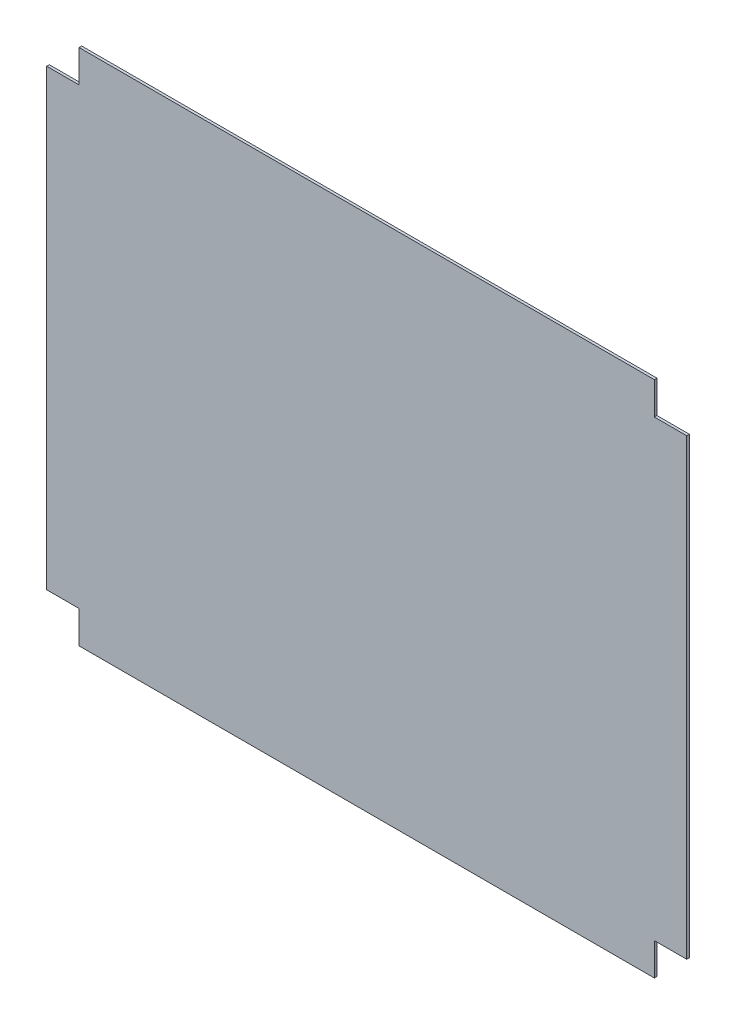
SolidWorks part; units mm, degrees
ref_plane "Front Plane" through (0, 0, 0) normal (0, 0, 1) x (1, 0, 0)
ref_plane "Top Plane" through (0, 0, 0) normal (0, 1, 0) x (1, 0, 0)
ref_plane "Right Plane" through (0, 0, 0) normal (1, 0, 0) x (0, 0, -1)
sketch "Çizim1" plane through (0, 0, 0) normal (0, 0, 1) x (1, 0, 0)
  line L1 (-247, 400) -> (247, 400)
  line L2 (-247, 400) -> (-247, 0)
  line L3 (-247, 0) -> (247, 0)
  line L4 (247, 400) -> (247, 0)
  point P4 (0, 0)
  dimension "D1" = 494
  dimension "D2" = 400
base flange "Taban-Flanş1" sketch "Çizim1" thickness 2 reverse thickness direction no parameters "D1"=0.7366
sketch "Çizim6" plane through (0, 0, 0) normal (0, 0, 1) x (1, 0, 0)
  line L0 (0, 0) -> (0, 141.4283) construction
  line L1 (-247, 400) -> (-222, 400)
  line L2 (-247, 400) -> (-247, 375)
  line L3 (-247, 375) -> (-222, 375)
  line L4 (-222, 400) -> (-222, 375)
  line L5 (-247, 200) -> (-327.7309, 200) construction
  line L6 (-247, 400) -> (-247, 0) construction
  line L7 (247, 400) -> (247, 375)
  line L8 (247, 400) -> (222, 400)
  line L9 (222, 400) -> (222, 375)
  line L10 (247, 375) -> (222, 375)
  line L11 (247, 25) -> (222, 25)
  line L12 (222, 0) -> (222, 25)
  line L13 (247, 0) -> (222, 0)
  line L14 (247, 0) -> (247, 25)
  line L15 (-222, 0) -> (-222, 25)
  line L16 (-247, 25) -> (-222, 25)
  line L17 (-247, 0) -> (-247, 25)
  line L18 (-247, 0) -> (-222, 0)
  dimension "D1" = 25
  dimension "D2" = 25
extrude "Kes-Ekstrüzyon1" cut sketch "Çizim6" against normal blind 10 normal cut yes
sketch "Büküm-Çizgileri1" [suppressed] plane through (0, 0, 0) normal (0, 1, 0) x (1, 0, 0)
sketch "Sınırlandırma-Kutusu1" [suppressed] plane through (0, 0, 0) normal (0, 1, 0) x (1, 0, 0)
sheet metal parameters "Sac-Levha1" thickness 2 parameters "D1"=0.7366
flat pattern "Düz-Çoğaltma1" [suppressed]
sketch "Büküm-Çizgileri2" plane through (0, 0, 0) normal (0, 1, 0) x (1, 0, 0)
sketch3d "Sınırlandırma-Kutusu2" [suppressed]
  line L0 (453, 0, 0) -> (-453, 0, 0) construction
  line L1 (453, 400, 0) -> (-453, 400, 0) construction
  line L2 (453, 0, 0) -> (453, 400, 0) construction
  line L3 (-453, 0, 0) -> (-453, 400, 0) construction
sheet metal parameters "Sac-Levha2" thickness 2 parameters "D1"=0.7366
flat pattern "Düz-Çoğaltma1"
sketch "Büküm-Çizgileri2" plane through (0, 0, 0) normal (0, 1, 0) x (1, 0, 0)
sketch3d "Sınırlandırma-Kutusu2" [suppressed]
  line L0 (-247, 0, 0) -> (247, 0, 0) construction
  line L1 (-247, 400, 0) -> (247, 400, 0) construction
  line L2 (-247, 0, 0) -> (-247, 400, 0) construction
  line L3 (247, 0, 0) -> (247, 400, 0) construction
